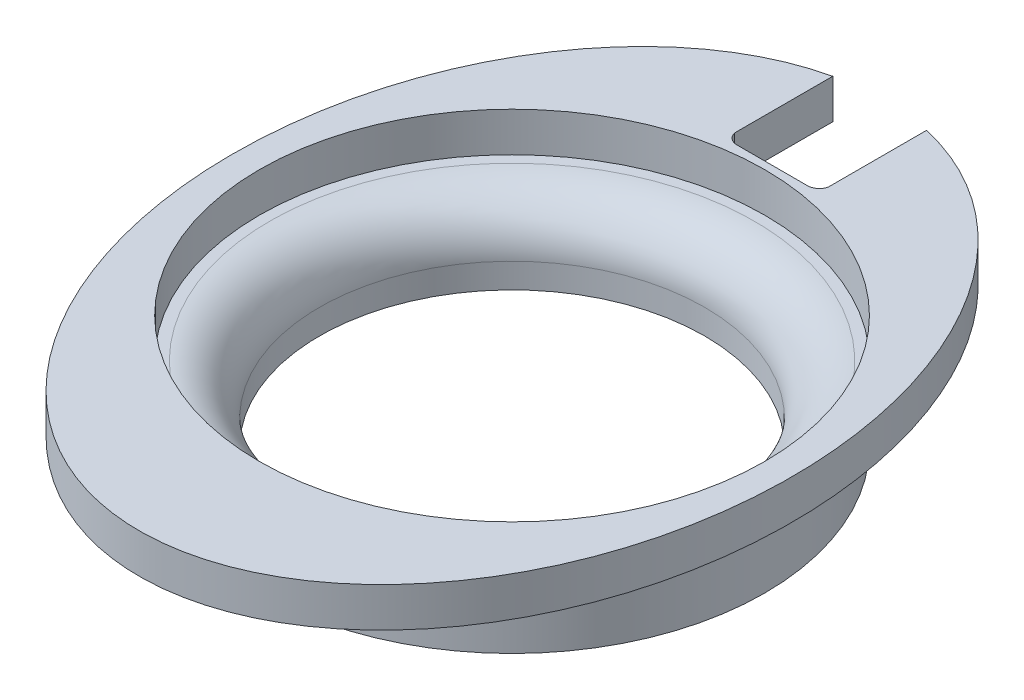
SolidWorks part; units mm, degrees
ref_plane "Front Plane" through (0, 0, 0) normal (0, 0, 1) x (1, 0, 0)
ref_plane "Top Plane" through (0, 0, 0) normal (0, 1, 0) x (1, 0, 0)
ref_plane "Right Plane" through (0, 0, 0) normal (1, 0, 0) x (0, 0, -1)
sketch "Sketch2" plane through (0, 0, 0) normal (0, 1, 0) x (1, 0, 0)
  line L0 (-3.7711, 29.5756) -> (-3.7711, 21.6756)
  line L1 (0, 41.7585) -> (0, 27.7685) construction
  line L2 (3.7711, 29.5756) -> (3.7711, 21.6756)
  line L3 (-2.664, 20.9325) -> (2.836, 20.9325)
  line L4 (-2.664, 20.9325) -> (-2.836, 20.9325)
  circle A1 centre (0, 0) radius 15.5
  circle A2 centre (0, 0) radius 20.335
  arc A3 (2.836, 20.9325) -> (3.7711, 21.6756) centre (2.836, 21.8925) ccw
  arc A4 (-2.836, 20.9325) -> (-3.7711, 21.6756) centre (-2.836, 21.8925) cw
  ellipse E0 centre (0, 0) end of major axis (0, -30) minor radius 22.5 (-3.7711, 29.5756) -> (3.7711, 29.5756) ccw
  point P18 (0.086, 20.9325)
  dimension "D1" = 60
  dimension "D2" = 31
  dimension "D4" = 40.67
  dimension "D6" = 0.96
  dimension "D3" = 45
  dimension "D5" = 5.5
  dimension "D7" = 0.086
  dimension "D8" = 3.7711
  dimension "D9" = 20.9325
extrude "Boss-Extrude1" add sketch "Sketch2" along normal blind 3.175 contours L0 E0 L2 A3 L3 L4 A4 A2 region at (-4.5177, 0, -25.6256)
extrude "Boss-Extrude2" add sketch "Sketch2<4>" against normal blind 6 separate body contours A2 A1 | A1 region at (0, 0, 0) region at (-19.7598, 0, 0)
sketch "Sketch2<4>" plane through (0, 0, 0) normal (0, 1, 0) x (1, 0, 0) same geometry as "Sketch2"
sketch "Sketch3" plane through (0, 0, 0) normal (0, 1, 0) x (1, 0, 0)
  circle A0 centre (0, 0) radius 15.5
  dimension "D1" = 31
extrude "Cut-Extrude1" cut sketch "Sketch3" against normal blind 6
fillet "Fillet2" radius 4 1 edges at (0, 0, 15.5)
